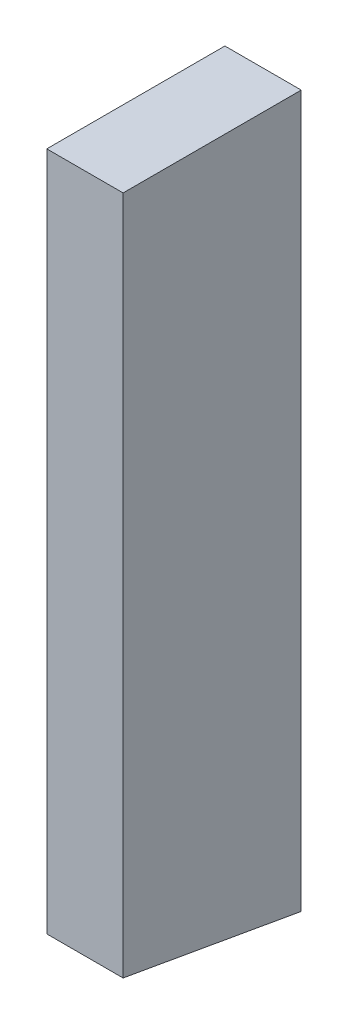
SolidWorks part; units mm, degrees
material "Pine"
ref_plane "Front Plane" through (0, 0, 0) normal (0, 0, 1) x (1, 0, 0)
ref_plane "Top Plane" through (0, 0, 0) normal (0, 1, 0) x (1, 0, 0)
ref_plane "Right Plane" through (0, 0, 0) normal (1, 0, 0) x (0, 0, -1)
sketch "Sketch1" plane through (0, 0, 0) normal (0, 1, 0) x (1, 0, 0)
  line L1 (-19.05, 44.45) -> (19.05, 44.45)
  line L2 (-19.05, 44.45) -> (-19.05, -44.45)
  line L4 (19.05, 44.45) -> (19.05, -44.45)
  line L5 (-19.05, 44.45) -> (19.05, -44.45) construction
  line L6 (-19.05, -44.45) -> (19.05, 44.45) construction
  line L7 (-19.05, -44.45) -> (19.05, -44.45)
  point P0 (0, 0)
  point P7 (20.6013, -43.586)
  point P8 (0, 0)
  point P10 (0, 0)
  point P11 (20.0486, -38.6163)
  point P12 (0, 0)
  dimension "D1" = 38.1
  dimension "D2" = 88.9
extrude "Boss-Extrude1" add sketch "Sketch1" along normal blind 355
sketch "Sketch2" plane through (-19.05, 0, 0) normal (-1, 0, 0) x (0, 0, 1)
  line L0 (-44.45, 0) -> (44.45, 15.6755)
  line L1 (44.45, 355) -> (44.45, 0) construction
  line L2 (44.45, 15.6755) -> (44.45, 0)
  line L3 (44.45, 0) -> (-44.45, 0)
  dimension "D1" = 10
extrude "Cut-Extrude1" cut sketch "Sketch2" against normal up to next
